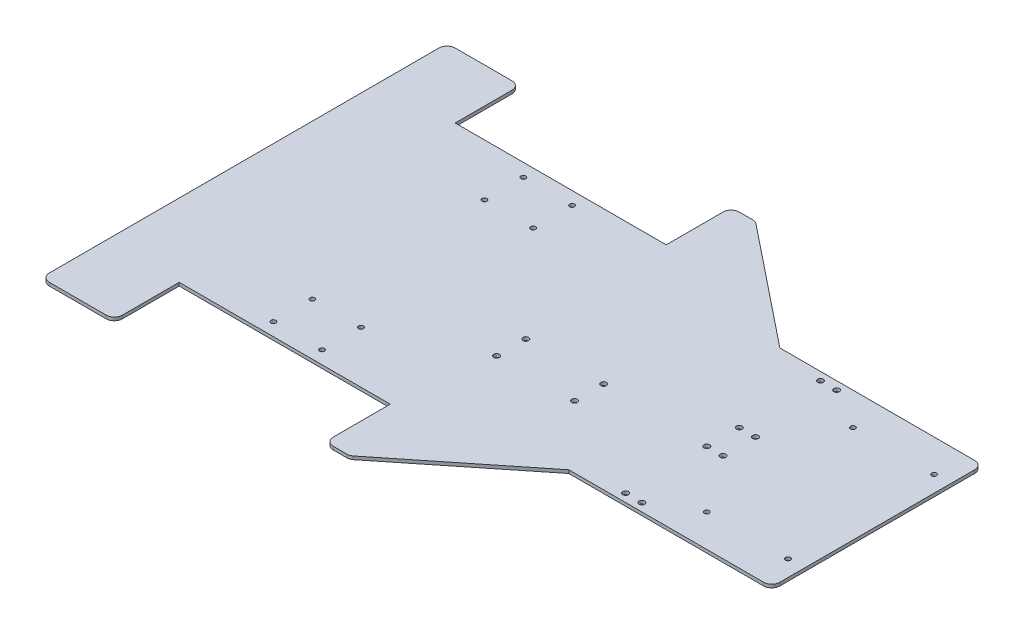
SolidWorks part; units mm, degrees
ref_plane "정면" through (0, 0, 0) normal (0, 0, 1) x (1, 0, 0)
ref_plane "윗면" through (0, 0, 0) normal (0, 1, 0) x (1, 0, 0)
ref_plane "우측면" through (0, 0, 0) normal (1, 0, 0) x (0, 0, -1)
sketch "스케치1" plane through (0, 0, 0) normal (0, 1, 0) x (1, 0, 0)
  line L1 (-195, -125) -> (195, -125)
  line L2 (-195, -125) -> (-195, 125)
  line L3 (-195, 125) -> (195, 125)
  line L4 (195, -125) -> (195, 125)
  line L5 (-195, -125) -> (195, 125) construction
  line L6 (-195, 125) -> (195, -125) construction
  point P0 (0, 0)
  dimension "D1" = 390
  dimension "D2" = 250
extrude "보스-돌출1" add sketch "스케치1" along normal blind 2
sketch "스케치2" plane through (0, 2, 0) normal (0, 1, 0) x (1, 0, 0)
  line L5 (195, 125) -> (-195, 125) construction
  line L6 (-150, 125) -> (-20, 125)
  line L7 (-150, 125) -> (-150, 85)
  line L8 (-150, 85) -> (-20, 85)
  line L9 (-20, 125) -> (-20, 85)
  line L10 (-150, -125) -> (-20, -125)
  line L11 (-150, -125) -> (-150, -85)
  line L12 (-150, -85) -> (-20, -85)
  line L13 (-20, -125) -> (-20, -85)
  line L14 (-195, -125) -> (195, -125) construction
  line L15 (70, 125) -> (195, 125)
  line L16 (70, 125) -> (70, 65)
  line L17 (70, 65) -> (195, 65)
  line L18 (195, 125) -> (195, 65)
  line L19 (70, -125) -> (195, -125)
  line L20 (70, -125) -> (70, -65)
  line L21 (70, -65) -> (195, -65)
  line L22 (195, -125) -> (195, -65)
  line L23 (195, -125) -> (195, 125) construction
  line L24 (-195, 125) -> (-195, -125) construction
  dimension "D1" = 130
  dimension "D2" = 40
  dimension "D3" = 40
  dimension "D4" = 60
  dimension "D5" = 60
  dimension "D6" = 45
  dimension "D7" = 125
extrude "컷-돌출1" cut sketch "스케치2" against normal blind 5
sketch "스케치3" plane through (0, 2, 0) normal (0, 1, 0) x (1, 0, 0)
  line L0 (-5, 125) -> (70, 65)
  line L2 (70, -65) -> (-5, -125)
  line L4 (-5, 125) -> (70, 125)
  line L5 (-5, -125) -> (70, -125)
  line L6 (70, -65) -> (70, -125)
  line L7 (70, 65) -> (70, 125)
  dimension "D1" = 75
  dimension "D2" = 75
extrude "컷-돌출2" cut sketch "스케치3" against normal blind 10
fillet "필렛1" radius 5 10 edges at (-20, 1, 125) (-20, 1, -125) (-5, 1, 125) (-5, 1, -125) (195, 1, -65) (195, 1, 65) (-195, 1, -125) (-195, 1, 125) (-150, 1, -125) (-150, 1, 125)
sketch "스케치4" plane through (0, 2, 0) normal (0, 1, 0) x (1, 0, 0)
  line L0 (-195, 0) -> (195, 0) construction
  line L1 (-100, 77) -> (-70, 77) construction
  line L2 (-100, 77) -> (-100, 53) construction
  line L3 (-100, 53) -> (-70, 53) construction
  line L4 (-70, 77) -> (-70, 53) construction
  line L5 (-100, 77) -> (-70, 53) construction
  line L6 (-100, 53) -> (-70, 77) construction
  line L7 (-195, 120) -> (-195, -120) construction
  line L8 (195, -60) -> (195, 60) construction
  line L9 (-150, 85) -> (-20, 85) construction
  line L10 (-100, -53) -> (-70, -77) construction
  line L11 (-100, -77) -> (-70, -53) construction
  line L12 (-70, -77) -> (-70, -53) construction
  line L13 (-100, -53) -> (-70, -53) construction
  line L14 (-100, -77) -> (-100, -53) construction
  line L15 (-100, -77) -> (-70, -77) construction
  line L17 (100, -60) -> (110, -60) construction
  line L18 (100, -60) -> (100, 60) construction
  line L19 (100, 60) -> (110, 60) construction
  line L20 (110, -60) -> (110, 60) construction
  line L21 (100, -60) -> (110, 60) construction
  line L22 (100, 60) -> (110, -60) construction
  line L23 (100, -10) -> (110, -10) construction
  line L24 (100, -10) -> (100, 10) construction
  line L25 (100, 10) -> (110, 10) construction
  line L26 (110, -10) -> (110, 10) construction
  line L27 (100, -10) -> (110, 10) construction
  line L28 (100, 10) -> (110, -10) construction
  circle A0 centre (-100, 77) radius 1.5
  circle A1 centre (-70, 77) radius 1.5
  circle A2 centre (-70, 53) radius 1.5
  circle A3 centre (-100, 53) radius 1.5
  circle A4 centre (-100, -53) radius 1.5
  circle A5 centre (-70, -53) radius 1.5
  circle A6 centre (-70, -77) radius 1.5
  circle A7 centre (-100, -77) radius 1.5
  circle A8 centre (100, 60) radius 1.75
  circle A9 centre (110, 60) radius 1.75
  circle A10 centre (100, 10) radius 1.75
  circle A11 centre (110, 10) radius 1.75
  circle A12 centre (100, -10) radius 1.75
  circle A13 centre (110, -10) radius 1.75
  circle A14 centre (100, -60) radius 1.75
  circle A15 centre (110, -60) radius 1.75
  point P0 (-85, 65)
  point P25 (-85, -65)
  point P26 (105, 0)
  point P31 (105, 0)
  dimension "D5" = 3
  dimension "D9" = 3.5
  dimension "D1" = 30
  dimension "D2" = 24
  dimension "D3" = 95
  dimension "D4" = 32
  dimension "D6" = 120
  dimension "D7" = 10
  dimension "D8" = 20
  dimension "D10" = 85
extrude "컷-돌출3" cut sketch "스케치4" against normal through all
sketch "스케치5" plane through (0, 2, 0) normal (0, 1, 0) x (1, 0, 0)
  line L0 (-20, -85) -> (-150, -85) construction
  line L1 (-13, -26.5) -> (35, -26.5) construction
  line L2 (-13, -26.5) -> (-13, -8.5) construction
  line L3 (-13, -8.5) -> (35, -8.5) construction
  line L4 (35, -26.5) -> (35, -8.5) construction
  line L5 (195, -60) -> (195, 60) construction
  circle A1 centre (-13, -8.5) radius 1.75
  circle A2 centre (35, -8.5) radius 1.75
  circle A3 centre (-13, -26.5) radius 1.75
  circle A4 centre (35, -26.5) radius 1.75
  dimension "D1" = 3.5
  dimension "D2" = 58.5
  dimension "D3" = 18
  dimension "D4" = 48
  dimension "D5" = 160
extrude "컷-돌출4" cut sketch "스케치5" against normal through all
sketch "스케치6" plane through (0, 2, 0) normal (0, 1, 0) x (1, 0, 0)
  line L0 (70, 65) -> (190, 65) construction
  line L1 (135, 45) -> (185, 45) construction
  line L2 (135, 45) -> (135, -45) construction
  line L3 (135, -45) -> (185, -45) construction
  line L4 (185, 45) -> (185, -45) construction
  line L5 (190, -65) -> (70, -65) construction
  line L6 (195, -60) -> (195, 60) construction
  circle A0 centre (135, 45) radius 1.5
  circle A1 centre (185, 45) radius 1.5
  circle A2 centre (135, -45) radius 1.5
  circle A3 centre (185, -45) radius 1.5
  dimension "D5" = 3
  dimension "D1" = 20
  dimension "D2" = 20
  dimension "D3" = 10
  dimension "D4" = 50
extrude "컷-돌출5" cut sketch "스케치6" against normal through all
